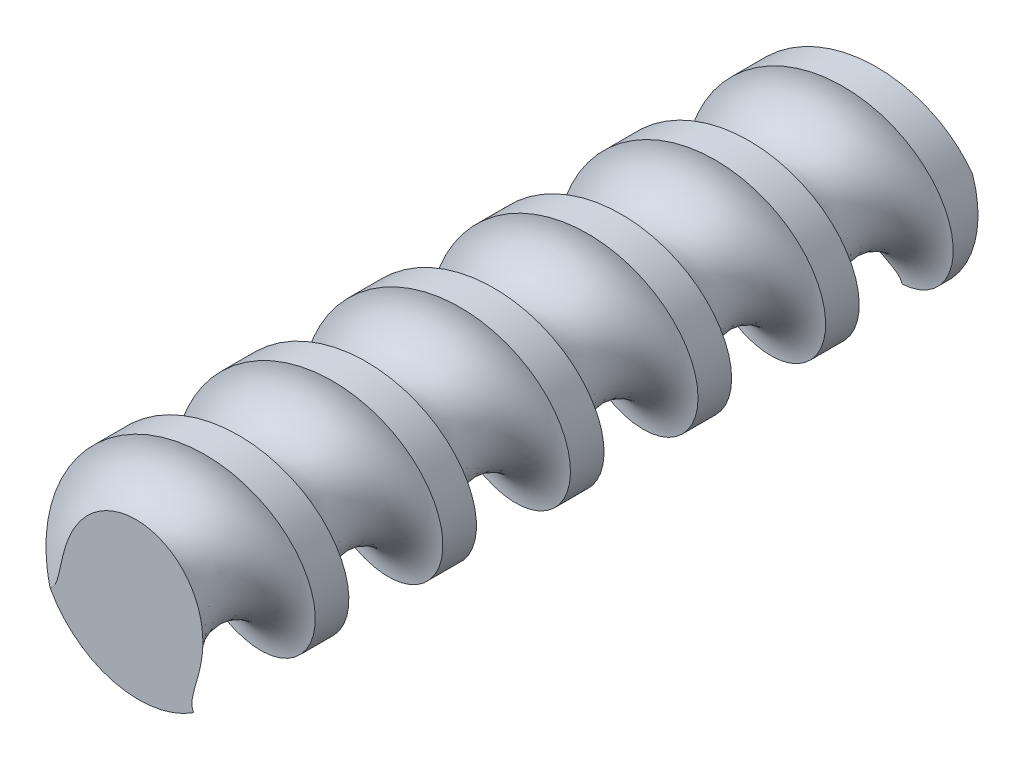
SolidWorks part; units mm, degrees
ref_plane "Спереди" through (0, 0, 0) normal (0, 0, 1) x (1, 0, 0)
ref_plane "Сверху" through (0, 0, 0) normal (0, 1, 0) x (1, 0, 0)
ref_plane "Справа" through (0, 0, 0) normal (1, 0, 0) x (0, 0, -1)
sketch "Эскиз1" plane through (0, 0, 0) normal (0, 0, 1) x (1, 0, 0)
  circle A0 centre (0, 0) radius 75
extrude "Бобышка-Вытянуть1" add sketch "Эскиз1" along normal blind 550
ref_plane "Плоскость1" through (0, 0, -40) normal (0, 0, -1) x (-1, 0, 0)
sketch "Эскиз3" plane through (0, 0, -40) normal (0, 0, -1) x (-1, 0, 0)
  circle A0 centre (0, 0) radius 75
curve "Спираль1" pitch 95 height 641.25 turns 6.75
sketch "Эскиз4" plane through (0, 0, 0) normal (0, 1, 0) x (1, 0, 0)
  line L0 (82.5, 40) -> (-82.5, 40) construction
  circle A0 centre (75, 40) radius 35
  spline S0 degree 3 poles (75, 40) (75, 39.185) (74.3435, 37.5521) (71.4148, 35.1051) (66.619, 32.6574) (60.0812, 30.2099) (51.9725, 27.7624) (42.505, 25.3149) (31.926, 22.8674) (20.5123, 20.4198) (8.5623, 17.9723) (-3.6116, 15.5248) (-15.6911, 13.0773) (-27.3603, 10.6298) (-38.3141, 8.1823) (-48.2661, 5.7347) (-56.9562, 3.2872) (-64.157, 0.8397) (-69.6803, -1.6078) (-73.3818, -4.0553) (-75.1645, -6.5029) (-74.9819, -8.9504) (-72.8389, -11.3979) (-68.7913, -13.8454) (-62.945, -16.2929) (-55.453, -18.7405) (-46.511, -21.188) (-36.353, -23.6355) (-25.2444, -26.083) (-13.4758, -28.5305) (-1.3548, -30.9781) (10.8016, -33.4256) (22.6756, -35.8731) (33.9567, -38.3206) (44.3499, -40.7681) (53.5835, -43.2156) (61.4161, -45.6632) (67.6429, -48.1107) (72.101, -50.5582) (74.674, -53.0057) (75.2944, -55.4532) (73.9462, -57.9008) (70.6645, -60.3483) (65.5352, -62.7958) (58.6923, -65.2433) (50.3149, -67.6908) (40.6219, -70.1384) (29.8667, -72.5859) (18.3307, -75.0334) (6.3153, -77.4809) (-5.8652, -79.9284) (-17.8923, -82.376) (-29.4516, -84.8235) (-40.2408, -87.271) (-49.9779, -89.7185) (-58.4082, -92.166) (-65.3113, -94.6135) (-70.5068, -97.0611) (-73.8587, -99.5086) (-75.2795, -101.9561) (-74.732, -104.4036) (-72.2305, -106.8511) (-67.8404, -109.2987) (-61.6765, -111.7462) (-53.9, -114.1937) (-44.7141, -116.6412) (-34.3592, -119.0887) (-23.1058, -121.5363) (-11.2484, -123.9838) (0.9032, -126.4313) (13.0312, -128.8788) (24.8184, -131.3263) (35.9568, -133.7739) (46.1549, -136.2214) (55.1463, -138.6689) (62.6958, -141.1164) (68.606, -143.5639) (72.7224, -146.0115) (74.9373, -148.459) (75.1929, -150.9065) (73.4825, -153.354) (69.8507, -155.8015) (64.3925, -158.249) (57.2507, -160.6966) (48.612, -163.1441) (38.7023, -165.5916) (27.7806, -168.0391) (16.1325, -170.4866) (4.0626, -172.9342) (-8.1135, -175.3817) (-20.0774, -177.8292) (-31.5164, -180.2767) (-42.1314, -182.7242) (-51.6447, -185.1718) (-59.8077, -187.6193) (-66.407, -190.0668) (-71.2699, -192.5143) (-74.2693, -194.9618) (-75.3269, -197.4094) (-74.4149, -199.8569) (-71.5572, -202.3044) (-66.8286, -204.7519) (-60.3526, -207.1994) (-52.2985, -209.6469) (-42.8771, -212.0945) (-32.3345, -214.542) (-20.9465, -216.9895) (-9.0108, -219.437) (3.1604, -221.8845) (15.2491, -224.3321) (26.939, -226.7796) (37.9246, -229.2271) (47.9185, -231.6746) (56.6596, -234.1221) (63.9192, -236.5697) (69.5075, -239.0172) (73.2784, -241.4647) (75.1334, -243.9122) (75.0239, -246.3597) (72.9527, -248.8073) (68.9741, -251.2548) (63.192, -253.7023) (55.7577, -256.1498) (46.8655, -258.5973) (36.7479, -261.0448) (25.6695, -263.4924) (13.9199, -265.9399) (1.8063, -268.3874) (-10.3545, -270.8349) (-22.2445, -273.2824) (-33.5529, -275.73) (-43.984, -278.1775) (-53.2651, -280.625) (-61.1535, -283.0725) (-67.4429, -285.52) (-71.969, -287.9676) (-74.6132, -290.4151) (-75.3066, -292.8626) (-74.031, -295.3101) (-70.8197, -297.7576) (-65.7567, -300.2052) (-58.9744, -302.6527) (-50.6501, -305.1002) (-41.0015, -307.5477) (-30.2808, -309.9952) (-18.7684, -312.4427) (-6.7652, -314.8903) (5.4148, -317.3378) (17.4533, -319.7853) (29.0354, -322.2328) (39.8583, -324.6803) (49.6391, -327.1279) (58.1219, -329.5754) (65.0851, -332.0229) (70.3465, -334.4704) (73.7686, -336.9179) (75.2619, -339.3655) (74.7874, -341.813) (72.3574, -344.2605) (68.0355, -346.708) (61.9347, -349.1555) (54.2145, -351.6031) (45.0768, -354.0506) (34.7605, -356.4981) (23.5353, -358.9456) (11.6947, -361.3931) (-0.4516, -363.8406) (-12.5861, -366.2882) (-24.3916, -368.7357) (-35.5593, -371.1832) (-45.7972, -373.6307) (-54.8377, -376.0782) (-62.4443, -378.5258) (-68.4183, -380.9733) (-72.6033, -383.4208) (-74.89, -385.8683) (-75.2186, -388.3158) (-73.5805, -390.7634) (-70.0185, -393.2109) (-64.6257, -395.6584) (-57.5432, -398.1059) (-48.9561, -400.5534) (-39.089, -403.001) (-28.1999, -405.4485) (-16.5734, -407.896) (-4.5135, -410.3435) (7.6643, -412.791) (19.6418, -415.2385) (31.1056, -417.6861) (41.7562, -420.1336) (51.315, -422.5811) (59.5321, -425.0286) (66.1926, -427.4761) (71.1224, -429.9237) (74.1926, -432.3712) (75.3228, -434.8187) (74.4837, -437.2662) (71.6971, -439.7137) (67.0358, -442.1613) (60.6217, -444.6088) (52.6226, -447.0563) (43.2476, -449.5038) (32.7418, -451.9513) (21.3799, -454.3989) (9.4591, -456.8464) (-2.7092, -459.2939) (-14.8065, -461.7414) (-26.5168, -464.1889) (-37.5337, -466.6365) (-47.5692, -469.084) (-56.361, -471.5315) (-63.6791, -473.979) (-69.3322, -476.4265) (-73.1725, -478.874) (-75.0996, -481.3216) (-75.0631, -483.7691) (-73.0639, -486.2166) (-69.1544, -488.6641) (-63.4367, -491.1116) (-56.0603, -493.5592) (-47.2182, -496.0067) (-37.1414, -498.4542) (-26.0936, -500.9017) (-14.3635, -503.3492) (-2.2578, -505.7968) (9.9069, -508.2443) (21.8126, -510.6918) (33.148, -513.1393) (43.6166, -515.5868) (52.9448, -518.0344) (60.8887, -520.4819) (67.2406, -522.9294) (71.8343, -525.3769) (74.5498, -527.8244) (75.3161, -530.2719) (74.1131, -532.7195) (70.9723, -535.167) (65.9758, -537.6145) (59.2543, -540.062) (50.9835, -542.5095) (41.3796, -544.9571) (30.6938, -547.4046) (19.2054, -549.8521) (7.2149, -552.2996) (-4.9643, -554.7471) (-17.0136, -557.1947) (-28.6181, -559.6422) (-39.4744, -562.0897) (-49.2985, -564.5372) (-57.8336, -566.9847) (-64.8566, -569.4323) (-70.1838, -571.8798) (-73.6759, -574.3273) (-75.2416, -576.7748) (-74.8401, -579.2223) (-72.4817, -581.6698) (-68.2281, -584.1174) (-62.1906, -586.5649) (-54.5271, -589.0124) (-45.4378, -591.4599) (-35.1606, -593.9074) (-23.9633, -596.3551) (-12.1426, -598.8021) (-4.0427, -600.435) (0, -601.25) knots 0 0 0 0 0.003817 0.007634 0.01145 0.015267 0.019084 0.022901 0.026718 0.030534 0.034351 0.038168 0.041985 0.045802 0.049618 0.053435 0.057252 0.061069 0.064885 0.068702 0.072519 0.076336 0.080153 0.083969 0.087786 0.091603 0.09542 0.099237 0.103053 0.10687 0.110687 0.114504 0.118321 0.122137 0.125954 0.129771 0.133588 0.137405 0.141221 0.145038 0.148855 0.152672 0.156489 0.160305 0.164122 0.167939 0.171756 0.175573 0.179389 0.183206 0.187023 0.19084 0.194656 0.198473 0.20229 0.206107 0.209924 0.21374 0.217557 0.221374 0.225191 0.229008 0.232824 0.236641 0.240458 0.244275 0.248092 0.251908 0.255725 0.259542 0.263359 0.267176 0.270992 0.274809 0.278626 0.282443 0.28626 0.290076 0.293893 0.29771 0.301527 0.305344 0.30916 0.312977 0.316794 0.320611 0.324427 0.328244 0.332061 0.335878 0.339695 0.343511 0.347328 0.351145 0.354962 0.358779 0.362595 0.366412 0.370229 0.374046 0.377863 0.381679 0.385496 0.389313 0.39313 0.396947 0.400763 0.40458 0.408397 0.412214 0.416031 0.419847 0.423664 0.427481 0.431298 0.435115 0.438931 0.442748 0.446565 0.450382 0.454198 0.458015 0.461832 0.465649 0.469466 0.473282 0.477099 0.480916 0.484733 0.48855 0.492366 0.496183 0.5 0.503817 0.507634 0.51145 0.515267 0.519084 0.522901 0.526718 0.530534 0.534351 0.538168 0.541985 0.545802 0.549618 0.553435 0.557252 0.561069 0.564885 0.568702 0.572519 0.576336 0.580153 0.583969 0.587786 0.591603 0.59542 0.599237 0.603053 0.60687 0.610687 0.614504 0.618321 0.622137 0.625954 0.629771 0.633588 0.637405 0.641221 0.645038 0.648855 0.652672 0.656489 0.660305 0.664122 0.667939 0.671756 0.675573 0.679389 0.683206 0.687023 0.69084 0.694656 0.698473 0.70229 0.706107 0.709924 0.71374 0.717557 0.721374 0.725191 0.729008 0.732824 0.736641 0.740458 0.744275 0.748092 0.751908 0.755725 0.759542 0.763359 0.767176 0.770992 0.774809 0.778626 0.782443 0.78626 0.790076 0.793893 0.79771 0.801527 0.805344 0.80916 0.812977 0.816794 0.820611 0.824427 0.828244 0.832061 0.835878 0.839695 0.843511 0.847328 0.851145 0.854962 0.858779 0.862595 0.866412 0.870229 0.874046 0.877863 0.881679 0.885496 0.889313 0.89313 0.896947 0.900763 0.90458 0.908397 0.912214 0.916031 0.919847 0.923664 0.927481 0.931298 0.935115 0.938931 0.942748 0.946565 0.950382 0.954198 0.958015 0.961832 0.965649 0.969466 0.973282 0.977099 0.980916 0.984733 0.98855 0.992366 0.996183 1 1 1 1 construction
sweep "Вырез-По траектории1" cut profiles "Эскиз4" path "Спираль1" align with end faces yes
